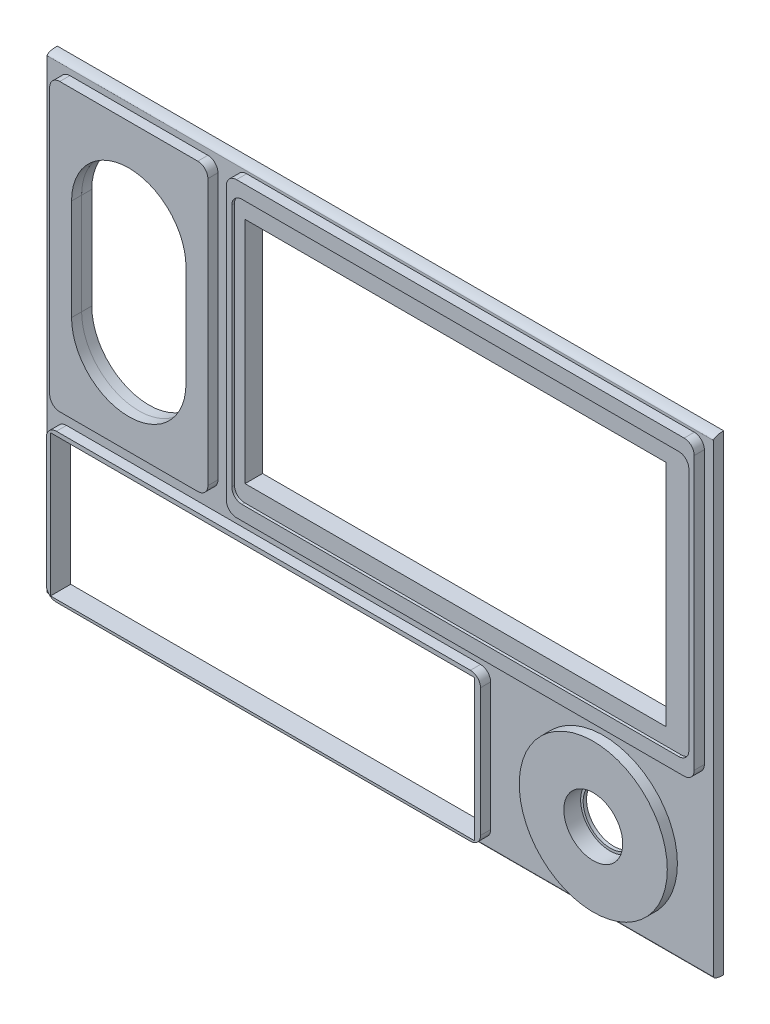
SolidWorks part; units mm, degrees
ref_plane "Front Plane" through (0, 0, 0) normal (0, 0, 1) x (1, 0, 0)
ref_plane "Top Plane" through (0, 0, 0) normal (0, 1, 0) x (1, 0, 0)
ref_plane "Right Plane" through (0, 0, 0) normal (1, 0, 0) x (0, 0, -1)
sketch "Sketch1" plane through (0, 0, 0) normal (0, 0, 1) x (1, 0, 0)
  line L1 (99, -70) -> (-99, -70)
  line L2 (99, -70) -> (99, 70)
  line L3 (99, 70) -> (-99, 70)
  line L4 (-99, -70) -> (-99, 70)
  line L5 (99, -70) -> (-99, 70) construction
  line L6 (99, 70) -> (-99, -70) construction
  point P0 (0, 0)
  dimension "D1" = 198
  dimension "D2" = 140
extrude "main_body" add sketch "Sketch1" along normal blind 3
fillet "long_corners" radius 3 2 edges at (0, 70, 3) (0, -70, 3) second distance 1 first distance on face at (0, 70, 1.5) first distance on face at (0, -70, 1.5)
sketch "Sketch2" plane through (0, 0, 3) normal (0, 0, 1) x (1, 0, 0)
  line L0 (-99, 24.75) -> (99, 24.75) construction
  line L1 (-99, 69) -> (-99, -69) construction
  line L2 (99, -69) -> (99, 69) construction
  line L3 (99, 69) -> (-99, 69) construction
  line L4 (-48.25, -17.75) -> (-95.25, -17.75)
  line L5 (-48.25, -17.75) -> (-48.25, 67.25)
  line L6 (-48.25, 67.25) -> (-95.25, 67.25)
  line L7 (-95.25, -17.75) -> (-95.25, 67.25)
  line L8 (-48.25, -17.75) -> (-95.25, 67.25) construction
  line L9 (-48.25, 67.25) -> (-95.25, -17.75) construction
  point P6 (-71.75, 24.75)
  dimension "D1" = 85
  dimension "D2" = 47
  dimension "D3" = 27.25
  dimension "D4" = 44.25
extrude "speaker" add sketch "Sketch2" along normal blind 3
fillet "speaker_corners" radius 3 4 edges at (-95.25, 67.25, 4.5) (-95.25, -17.75, 4.5) (-48.25, -17.75, 4.5) (-48.25, 67.25, 4.5)
sketch "Sketch3" plane through (0, 0, 3) normal (0, 0, 1) x (1, 0, 0)
  line L0 (-99, 24.75) -> (99, 24.75) construction
  line L1 (-99, 69) -> (-99, -69) construction
  line L2 (99, -69) -> (99, 69) construction
  line L4 (-48.25, -14.75) -> (-48.25, 64.25) construction
  line L5 (96.25, -18.75) -> (-42.75, -18.75)
  line L6 (96.25, -18.75) -> (96.25, 68.25)
  line L7 (96.25, 68.25) -> (-42.75, 68.25)
  line L8 (-42.75, -18.75) -> (-42.75, 68.25)
  line L9 (96.25, -18.75) -> (-42.75, 68.25) construction
  line L10 (96.25, 68.25) -> (-42.75, -18.75) construction
  line L11 (99, 70) -> (-99, 70) construction
  point P8 (26.75, 24.75)
  dimension "D1" = 1.75
  dimension "D2" = 87
  dimension "D3" = 139
  dimension "D4" = 2.75
  dimension "D5" = 5.5
extrude "lcd" add sketch "Sketch3" along normal blind 3
fillet "lcd_corners" radius 3 4 edges at (96.25, -18.75, 4.5) (-42.75, -18.75, 4.5) (96.25, 68.25, 4.5) (-42.75, 68.25, 4.5)
sketch "Sketch4" plane through (0, 0, 3) normal (0, 0, 1) x (1, 0, 0)
  line L0 (-99, -45.25) -> (99, -45.25) construction
  line L1 (-99, 69) -> (-99, -69) construction
  line L2 (99, -69) -> (99, 69) construction
  line L4 (-92.25, -17.75) -> (-51.25, -17.75) construction
  line L5 (32.75, -67.25) -> (-96.25, -67.25)
  line L6 (32.75, -67.25) -> (32.75, -23.25)
  line L7 (32.75, -23.25) -> (-96.25, -23.25)
  line L8 (-96.25, -67.25) -> (-96.25, -23.25)
  line L9 (32.75, -67.25) -> (-96.25, -23.25) construction
  line L10 (32.75, -23.25) -> (-96.25, -67.25) construction
  line L11 (-99, -70) -> (99, -70) construction
  point P8 (-31.75, -45.25)
  dimension "D1" = 2.75
  dimension "D2" = 129
  dimension "D3" = 44
  dimension "D4" = 2.75
  dimension "D5" = 5.5
extrude "keypad" add sketch "Sketch4" along normal blind 3
fillet "keypad_corners" radius 3 4 edges at (-96.25, -67.25, 4.5) (32.75, -67.25, 4.5) (32.75, -23.25, 4.5) (-96.25, -23.25, 4.5)
sketch "Sketch5" plane through (0, 0, 3) normal (0, 0, 1) x (1, 0, 0)
  line L0 (32.75, -45.25) -> (99, -45.25) construction
  line L1 (32.75, -64.25) -> (32.75, -26.25) construction
  line L2 (99, -69) -> (99, 69) construction
  circle A0 centre (66.25, -45.25) radius 22
  dimension "D1" = 44
  dimension "D2" = 32.75
  dimension "D3" = 33.5
extrude "vfo" add sketch "Sketch5" along normal blind 3
sketch "Sketch6" plane through (0, 0, 6) normal (0, 0, 1) x (1, 0, 0)
  line L0 (44.25, -45.25) -> (88.25, -45.25) construction
  line L2 (66.25, -23.25) -> (66.25, -67.25) construction
  line L3 (74.5, -56.25) -> (58, -56.25)
  line L4 (74.5, -56.25) -> (74.5, -34.25)
  line L5 (74.5, -34.25) -> (58, -34.25)
  line L6 (58, -56.25) -> (58, -34.25)
  line L7 (74.5, -56.25) -> (58, -34.25) construction
  line L8 (74.5, -34.25) -> (58, -56.25) construction
  circle A0 centre (66.25, -45.25) radius 22 construction
  point P7 (66.25, -45.25)
  dimension "D1" = 16.5
  dimension "D2" = 22
sketch "Sketch7" plane through (0, 0, 6) normal (0, 0, 1) x (1, 0, 0)
  line L0 (44.25, -45.25) -> (88.25, -45.25) construction
  line L1 (66.25, -23.25) -> (66.25, -67.25) construction
  circle A0 centre (66.25, -45.25) radius 22 construction
  circle A1 centre (66.25, -45.25) radius 22 construction
  circle A2 centre (66.25, -45.25) radius 8.75
  dimension "D1" = 17.5
extrude "vfo_encoder_knob_cut" cut sketch "Sketch7" against normal blind 5
sketch "Sketch16" plane through (0, 0, 0) normal (0, 0, -1) x (-1, 0, 0)
  line L0 (-99, 70) -> (99, 70) construction
  line L5 (-99, -19) -> (99, -19) construction
  line L10 (-99, -70) -> (-99, 70) construction
  line L27 (99, 70) -> (99, -70) construction
  line L28 (99, -70) -> (-99, -70) construction
  line L30 (-43, -21) -> (-69, -21)
  line L31 (-43, -21) -> (-43, -17)
  line L32 (-43, -17) -> (-69, -17)
  line L33 (-69, -21) -> (-69, -17)
  line L34 (-43, -21) -> (-69, -17) construction
  line L35 (-43, -17) -> (-69, -21) construction
  line L36 (-86.25, -23) -> (-43, -23)
  line L37 (-86.25, -23) -> (-86.25, -32)
  line L38 (-86.25, -32) -> (-43, -32)
  line L39 (-43, -23) -> (-43, -32)
  line L40 (-55, -33.25) -> (-43, -33.25)
  line L41 (-55, -33.25) -> (-55, -57.25)
  line L42 (-55, -57.25) -> (-43, -57.25)
  line L43 (-43, -33.25) -> (-43, -57.25)
  line L44 (-42, -17) -> (-32, -17)
  line L45 (-42, -17) -> (-42, -57.25)
  line L46 (-42, -57.25) -> (-32, -57.25)
  line L47 (-32, -17) -> (-32, -57.25)
  line L48 (-86.25, -33.25) -> (-77.25, -33.25)
  line L49 (-86.25, -33.25) -> (-86.25, -57.25)
  line L50 (-86.25, -57.25) -> (-77.25, -57.25)
  line L51 (-77.25, -33.25) -> (-77.25, -57.25)
  line L52 (-93, 45) -> (-87, 45)
  line L53 (-93, 45) -> (-93, 33.5)
  line L54 (-93, 33.5) -> (-87, 33.5)
  line L55 (-87, 45) -> (-87, 33.5)
  point P30 (-56, -19)
  dimension "D4" = 6
  dimension "D5" = 25
  dimension "D6" = 6
  dimension "D13" = 11.5
  dimension "D16" = 51
  dimension "D17" = 26
  dimension "D18" = 4
  dimension "D19" = 142
  dimension "D20" = 40.25
  dimension "D21" = 24
  dimension "D22" = 12.75
  dimension "D23" = 12.75
  dimension "D24" = 12
  dimension "D25" = 10
  dimension "D26" = 1
  dimension "D27" = 12.75
  dimension "D28" = 22.25
  dimension "D29" = 9
  dimension "D30" = 43.25
  dimension "D31" = 1.25
  dimension "D32" = 12.75
  dimension "D33" = 24
  dimension "D34" = 9
  dimension "D35" = 1
extrude "conn_slots" [suppressed] cut sketch "Sketch16" against normal blind 2
sketch "Sketch19" plane through (0, 0, 6) normal (0, 0, 1) x (1, 0, 0)
  line L0 (-71.75, 67.25) -> (-71.75, -17.75) construction
  line L1 (-51.25, 67.25) -> (-92.25, 67.25) construction
  line L2 (-92.25, -17.75) -> (-51.25, -17.75) construction
  line L3 (-71.75, 8.25) -> (-71.75, 38.25) construction
  line L4 (-95.25, 64.25) -> (-95.25, -14.75) construction
  line L5 (-95.25, 24.75) -> (-48.25, 24.75) construction
  line L6 (-48.25, -14.75) -> (-48.25, 64.25) construction
  line L7 (-88.75, 8.25) -> (-88.75, 38.25)
  line L8 (-54.75, 8.25) -> (-54.75, 38.25)
  arc A0 (-88.75, 8.25) -> (-54.75, 8.25) centre (-71.75, 8.25) ccw
  arc A1 (-54.75, 38.25) -> (-88.75, 38.25) centre (-71.75, 38.25) ccw
  point P14 (-71.75, 23.25)
  point P19 (-71.75, -8.75)
  point P20 (-71.75, 55.25)
  dimension "D2" = 64
  dimension "D1" = 34
  dimension "D3" = 12
extrude "speaker_cut" cut sketch "Sketch19" against normal through all
sketch "Sketch21" plane through (0, 0, 0) normal (0, 0, -1) x (-1, 0, 0)
  line L0 (71.75, -8.75) -> (71.75, 55.25) construction
  line L2 (54.75, 8.25) -> (54.75, 38.25) construction
  line L3 (54.75, 23.25) -> (88.75, 23.25) construction
  line L4 (88.75, 38.25) -> (88.75, 8.25) construction
  line L5 (50.25, 59.25) -> (93.25, 59.25)
  line L6 (50.25, 59.25) -> (50.25, -12.75)
  line L7 (50.25, -12.75) -> (93.25, -12.75)
  line L8 (93.25, 59.25) -> (93.25, -12.75)
  line L9 (50.25, 59.25) -> (93.25, -12.75) construction
  line L10 (50.25, -12.75) -> (93.25, 59.25) construction
  arc A0 (54.75, 8.25) -> (88.75, 8.25) centre (71.75, 8.25) ccw construction
  arc A1 (88.75, 38.25) -> (54.75, 38.25) centre (71.75, 38.25) ccw construction
  point P14 (71.75, 23.25)
  dimension "D1" = 43
  dimension "D2" = 72
extrude "speaker_slot" cut sketch "Sketch21" against normal blind 3
sketch "Sketch9" plane through (0, 0, 6) normal (0, 0, 1) x (1, 0, 0)
  line L0 (-42.75, 24.75) -> (96.25, 24.75) construction
  line L1 (-42.75, 65.25) -> (-42.75, -15.75) construction
  line L2 (96.25, -15.75) -> (96.25, 65.25) construction
  line L3 (-39.75, -18.75) -> (93.25, -18.75) construction
  line L4 (94.65, -14.5) -> (-41.15, -14.5)
  line L5 (94.65, -14.5) -> (94.65, 64)
  line L6 (94.65, 64) -> (-41.15, 64)
  line L7 (-41.15, -14.5) -> (-41.15, 64)
  line L8 (94.65, -14.5) -> (-41.15, 64) construction
  line L9 (94.65, 64) -> (-41.15, -14.5) construction
  line L10 (93.25, 68.25) -> (-39.75, 68.25) construction
  line L11 (96.25, -15.75) -> (96.25, 65.25) construction
  point P6 (26.75, 24.75)
  dimension "D1" = 135.8
  dimension "D2" = 78.5
  dimension "D3" = 1.6
  dimension "D4" = 4.25
  dimension "D5" = 4.25
  dimension "D6" = 1.6
extrude "lcd_front" cut sketch "Sketch9" against normal blind 0.8
sketch "Sketch10" plane through (0, 0, 0) normal (0, 0, -1) x (-1, 0, 0)
  line L0 (-94.65, -14.5) -> (-94.65, 64) construction
  line L1 (-94.65, 64) -> (41.15, 64) construction
  line L2 (41.15, 64) -> (41.15, -14.5) construction
  line L3 (-94.65, 64) -> (41.15, 64) construction
  line L4 (38, -9.5) -> (-87, -9.5)
  line L5 (38, -9.5) -> (38, 58.5)
  line L6 (38, 58.5) -> (-87, 58.5)
  line L7 (-87, -9.5) -> (-87, 58.5)
  line L8 (-87, -9.5) -> (38, 58.5) construction
  line L9 (-87, 58.5) -> (38, -9.5) construction
  line L10 (-99, -70) -> (-99, 70) construction
  line L11 (-99, 70) -> (99, 70) construction
  line L13 (41.15, -14.5) -> (-94.65, -14.5) construction
  dimension "D1" = 125
  dimension "D2" = 68
  dimension "D3" = 12
  dimension "D4" = 3.15
  dimension "D5" = 11.5
  dimension "D6" = 5.5
  dimension "D7" = 7.65
  dimension "D8" = 5.5
  dimension "D9" = 5
fillet "speaker_slot_corners" [suppressed] radius 3
sketch "Sketch24" plane through (0, 0, 3) normal (0, 0, 1) x (1, 0, 0)
  line L0 (99, -69) -> (99, 69) construction
  line L1 (99, 68.5) -> (98, 68.5)
  line L2 (99, 68.5) -> (99, -67.5)
  line L3 (99, -67.5) -> (98, -67.5)
  line L4 (98, 68.5) -> (98, -67.5)
  line L5 (-99, -69) -> (99, -69) construction
  line L6 (-98, -69) -> (98, -69)
  line L7 (-98, -69) -> (-98, -68)
  line L8 (-98, -68) -> (98, -68)
  line L9 (98, -69) -> (98, -68)
  line L10 (-99, 69) -> (-99, -69) construction
  line L12 (-99, 69) -> (-98, 69)
  line L13 (-99, 69) -> (-99, -67)
  line L14 (-99, -67) -> (-98, -67)
  line L15 (-98, 69) -> (-98, -67)
  line L16 (38, -19.5) -> (39, -19.5)
  line L17 (38, -19.5) -> (38, -67.5)
  line L18 (38, -67.5) -> (39, -67.5)
  line L19 (39, -19.5) -> (39, -67.5)
  line L20 (92, -19.5) -> (93, -19.5)
  line L21 (92, -19.5) -> (92, -67.5)
  line L22 (92, -67.5) -> (93, -67.5)
  line L23 (93, -19.5) -> (93, -67.5)
  dimension "D1" = 196
  dimension "D2" = 1
  dimension "D3" = 136
  dimension "D4" = 1
  dimension "D5" = 1
  dimension "D6" = 1.5
  dimension "D7" = 136
  dimension "D8" = 1
  dimension "D9" = 1
  dimension "D10" = 1
  dimension "D11" = 48
  dimension "D12" = 48
  dimension "D13" = 1.5
  dimension "D14" = 1.5
  dimension "D15" = 6
  dimension "D16" = 60
extrude "3D_supports" [suppressed] add sketch "Sketch24" along normal blind 3
sketch "Sketch25" plane through (0, 0, 6) normal (0, 0, 1) x (1, 0, 0)
  line L0 (-96.25, -30.25) -> (32.75, -30.25) construction
  line L1 (29.75, -23.25) -> (-93.25, -23.25) construction
  line L2 (-93.25, -67.25) -> (29.75, -67.25) construction
  line L3 (-77, -23.25) -> (-77, -67.25) construction
  line L5 (-35.4, -64) -> (32.75, -64) construction
  line L6 (-96.25, -26.25) -> (-96.25, -64.25) construction
  line L11 (32.75, -64.25) -> (32.75, -26.25) construction
  line L12 (-58.7, -23.25) -> (-58.7, -67.25) construction
  line L13 (-96.25, -40.25) -> (32.75, -40.25) construction
  line L14 (29.75, -23.25) -> (-93.25, -23.25) construction
  line L15 (-40.4, -23.25) -> (-40.4, -67.25) construction
  line L16 (-93.25, -67.25) -> (29.75, -67.25) construction
  line L17 (-72, -34) -> (-82, -34)
  line L18 (-22.1, -23.25) -> (-22.1, -67.25) construction
  line L19 (-96.25, -50.25) -> (32.75, -50.25) construction
  line L20 (-3.8, -23.25) -> (-3.8, -67.25) construction
  line L21 (-72, -34) -> (-72, -26.5)
  line L22 (14.5, -23.25) -> (14.5, -67.25) construction
  line L23 (-96.25, -26.25) -> (-96.25, -64.25) construction
  line L24 (-96.25, -60.25) -> (32.75, -60.25) construction
  line L25 (-72, -26.5) -> (-82, -26.5)
  line L26 (-82, -34) -> (-82, -26.5)
  line L27 (-72, -34) -> (-82, -26.5) construction
  line L28 (-72, -26.5) -> (-82, -34) construction
  line L29 (-72, -44) -> (-82, -44)
  line L30 (-72, -44) -> (-72, -36.5)
  line L31 (-72, -36.5) -> (-82, -36.5)
  line L32 (-82, -44) -> (-82, -36.5)
  line L33 (-72, -44) -> (-82, -36.5) construction
  line L34 (-72, -36.5) -> (-82, -44) construction
  line L35 (-72, -54) -> (-82, -54)
  line L36 (-72, -54) -> (-72, -46.5)
  line L37 (-72, -46.5) -> (-82, -46.5)
  line L38 (-82, -54) -> (-82, -46.5)
  line L39 (-72, -54) -> (-82, -46.5) construction
  line L40 (-72, -46.5) -> (-82, -54) construction
  line L41 (-72, -64) -> (-82, -64)
  line L42 (-72, -64) -> (-72, -56.5)
  line L43 (-72, -56.5) -> (-82, -56.5)
  line L44 (-82, -64) -> (-82, -56.5)
  line L45 (-72, -64) -> (-82, -56.5) construction
  line L46 (-72, -56.5) -> (-82, -64) construction
  line L47 (-53.7, -34) -> (-63.7, -34)
  line L48 (-53.7, -34) -> (-53.7, -26.5)
  line L49 (-53.7, -26.5) -> (-63.7, -26.5)
  line L50 (-63.7, -34) -> (-63.7, -26.5)
  line L51 (-53.7, -34) -> (-63.7, -26.5) construction
  line L52 (-53.7, -26.5) -> (-63.7, -34) construction
  line L53 (-53.7, -44) -> (-63.7, -44)
  line L54 (-53.7, -44) -> (-53.7, -36.5)
  line L55 (-53.7, -36.5) -> (-63.7, -36.5)
  line L56 (-63.7, -44) -> (-63.7, -36.5)
  line L57 (-53.7, -44) -> (-63.7, -36.5) construction
  line L58 (-53.7, -36.5) -> (-63.7, -44) construction
  line L59 (-53.7, -54) -> (-63.7, -54)
  line L60 (-53.7, -54) -> (-53.7, -46.5)
  line L61 (-53.7, -46.5) -> (-63.7, -46.5)
  line L62 (-63.7, -54) -> (-63.7, -46.5)
  line L63 (-53.7, -54) -> (-63.7, -46.5) construction
  line L64 (-53.7, -46.5) -> (-63.7, -54) construction
  line L65 (-53.7, -64) -> (-63.7, -64)
  line L66 (-53.7, -64) -> (-53.7, -56.5)
  line L67 (-53.7, -56.5) -> (-63.7, -56.5)
  line L68 (-63.7, -64) -> (-63.7, -56.5)
  line L69 (-53.7, -64) -> (-63.7, -56.5) construction
  line L70 (-53.7, -56.5) -> (-63.7, -64) construction
  line L71 (-35.4, -34) -> (-45.4, -34)
  line L72 (-35.4, -34) -> (-35.4, -26.5)
  line L73 (-35.4, -26.5) -> (-45.4, -26.5)
  line L74 (-45.4, -34) -> (-45.4, -26.5)
  line L75 (-35.4, -34) -> (-45.4, -26.5) construction
  line L76 (-35.4, -26.5) -> (-45.4, -34) construction
  line L77 (-35.4, -44) -> (-45.4, -44)
  line L78 (-35.4, -44) -> (-35.4, -36.5)
  line L79 (-35.4, -36.5) -> (-45.4, -36.5)
  line L80 (-45.4, -44) -> (-45.4, -36.5)
  line L81 (-35.4, -44) -> (-45.4, -36.5) construction
  line L82 (-35.4, -36.5) -> (-45.4, -44) construction
  line L83 (-35.4, -54) -> (-45.4, -54)
  line L84 (-35.4, -54) -> (-35.4, -46.5)
  line L85 (-35.4, -46.5) -> (-45.4, -46.5)
  line L86 (-45.4, -54) -> (-45.4, -46.5)
  line L87 (-35.4, -54) -> (-45.4, -46.5) construction
  line L88 (-35.4, -46.5) -> (-45.4, -54) construction
  line L89 (-35.4, -64) -> (-45.4, -64)
  line L90 (-35.4, -64) -> (-35.4, -56.5)
  line L91 (-35.4, -56.5) -> (-45.4, -56.5)
  line L92 (-45.4, -64) -> (-45.4, -56.5)
  line L93 (-35.4, -64) -> (-45.4, -56.5) construction
  line L94 (-35.4, -56.5) -> (-45.4, -64) construction
  line L95 (-17.1, -34) -> (-27.1, -34)
  line L96 (-17.1, -34) -> (-17.1, -26.5)
  line L97 (-17.1, -26.5) -> (-27.1, -26.5)
  line L98 (-27.1, -34) -> (-27.1, -26.5)
  line L99 (-17.1, -34) -> (-27.1, -26.5) construction
  line L100 (-17.1, -26.5) -> (-27.1, -34) construction
  line L101 (-17.1, -44) -> (-27.1, -44)
  line L102 (-17.1, -44) -> (-17.1, -36.5)
  line L103 (-17.1, -36.5) -> (-27.1, -36.5)
  line L104 (-27.1, -44) -> (-27.1, -36.5)
  line L105 (-17.1, -44) -> (-27.1, -36.5) construction
  line L106 (-17.1, -36.5) -> (-27.1, -44) construction
  line L111 (-17.1, -54) -> (-27.1, -54)
  line L112 (-17.1, -54) -> (-17.1, -46.5)
  line L113 (-17.1, -46.5) -> (-27.1, -46.5)
  line L114 (-27.1, -54) -> (-27.1, -46.5)
  line L115 (-17.1, -54) -> (-27.1, -46.5) construction
  line L116 (-17.1, -46.5) -> (-27.1, -54) construction
  line L117 (-17.1, -64) -> (-27.1, -64)
  line L118 (-17.1, -64) -> (-17.1, -56.5)
  line L119 (-17.1, -56.5) -> (-27.1, -56.5)
  line L120 (-27.1, -64) -> (-27.1, -56.5)
  line L121 (-17.1, -64) -> (-27.1, -56.5) construction
  line L122 (-17.1, -56.5) -> (-27.1, -64) construction
  line L127 (1.2, -34) -> (-8.8, -34)
  line L128 (1.2, -34) -> (1.2, -26.5)
  line L129 (1.2, -26.5) -> (-8.8, -26.5)
  line L130 (-8.8, -34) -> (-8.8, -26.5)
  line L131 (1.2, -34) -> (-8.8, -26.5) construction
  line L132 (1.2, -26.5) -> (-8.8, -34) construction
  line L133 (19.5, -34) -> (9.5, -34)
  line L134 (19.5, -34) -> (19.5, -26.5)
  line L135 (19.5, -26.5) -> (9.5, -26.5)
  line L136 (9.5, -34) -> (9.5, -26.5)
  line L137 (19.5, -34) -> (9.5, -26.5) construction
  line L138 (19.5, -26.5) -> (9.5, -34) construction
  line L139 (1.2, -44) -> (-8.8, -44)
  line L140 (1.2, -44) -> (1.2, -36.5)
  line L141 (1.2, -36.5) -> (-8.8, -36.5)
  line L142 (-8.8, -44) -> (-8.8, -36.5)
  line L143 (1.2, -44) -> (-8.8, -36.5) construction
  line L144 (1.2, -36.5) -> (-8.8, -44) construction
  line L145 (19.5, -44) -> (9.5, -44)
  line L146 (19.5, -44) -> (19.5, -36.5)
  line L147 (19.5, -36.5) -> (9.5, -36.5)
  line L148 (9.5, -44) -> (9.5, -36.5)
  line L149 (19.5, -44) -> (9.5, -36.5) construction
  line L150 (19.5, -36.5) -> (9.5, -44) construction
  line L151 (19.5, -54) -> (9.5, -54)
  line L152 (19.5, -54) -> (19.5, -46.5)
  line L153 (19.5, -46.5) -> (9.5, -46.5)
  line L154 (9.5, -54) -> (9.5, -46.5)
  line L155 (19.5, -54) -> (9.5, -46.5) construction
  line L156 (19.5, -46.5) -> (9.5, -54) construction
  line L157 (19.5, -64) -> (9.5, -64)
  line L158 (19.5, -64) -> (19.5, -56.5)
  line L159 (19.5, -56.5) -> (9.5, -56.5)
  line L160 (9.5, -64) -> (9.5, -56.5)
  line L161 (19.5, -64) -> (9.5, -56.5) construction
  line L162 (19.5, -56.5) -> (9.5, -64) construction
  line L163 (1.2, -64) -> (-8.8, -64)
  line L164 (1.2, -64) -> (1.2, -46.5)
  line L165 (1.2, -46.5) -> (-8.8, -46.5)
  line L166 (-8.8, -64) -> (-8.8, -46.5)
  line L167 (1.2, -64) -> (-8.8, -46.5) construction
  line L168 (1.2, -46.5) -> (-8.8, -64) construction
  point P34 (-77, -30.25)
  point P39 (-77, -40.25)
  point P44 (-77, -50.25)
  point P49 (-77, -60.25)
  point P54 (-58.7, -30.25)
  point P59 (-58.7, -40.25)
  point P64 (-58.7, -50.25)
  point P69 (-58.7, -60.25)
  point P74 (-40.4, -30.25)
  point P79 (-40.4, -40.25)
  point P84 (-40.4, -50.25)
  point P89 (-40.4, -60.25)
  point P94 (-22.1, -30.25)
  point P99 (-22.1, -40.25)
  point P104 (-22.1, -50.25)
  point P109 (-22.1, -60.25)
  point P114 (-3.8, -30.25)
  point P119 (14.5, -30.25)
  point P124 (-3.8, -40.25)
  point P129 (14.5, -40.25)
  point P134 (14.5, -50.25)
  point P139 (14.5, -60.25)
  point P144 (-3.8, -55.25)
  dimension "D1" = 18.25
  dimension "D2" = 18.3
  dimension "D3" = 18.3
  dimension "D4" = 18.3
  dimension "D5" = 18.3
  dimension "D6" = 18.3
  dimension "D7" = 19.25
  dimension "D8" = 7
  dimension "D9" = 10
  dimension "D10" = 10
  dimension "D11" = 10
  dimension "D12" = 7
  dimension "D13" = 10
  dimension "D14" = 10
  dimension "D15" = 10
  dimension "D16" = 10
  dimension "D17" = 10
  dimension "D18" = 10
  dimension "D19" = 10
  dimension "D20" = 10
  dimension "D21" = 10
  dimension "D22" = 10
  dimension "D23" = 10
  dimension "D24" = 10
  dimension "D25" = 10
  dimension "D26" = 10
  dimension "D27" = 10
  dimension "D28" = 10
  dimension "D29" = 10
  dimension "D30" = 10
  dimension "D31" = 10
  dimension "D32" = 10
  dimension "D33" = 10
  dimension "D34" = 10
  dimension "D35" = 10
  dimension "D36" = 7.5
  dimension "D37" = 7.5
  dimension "D38" = 7.5
  dimension "D39" = 7.5
  dimension "D40" = 7.5
  dimension "D41" = 7.5
  dimension "D42" = 17.5
  dimension "D43" = 7.5
  dimension "D44" = 7.5
  dimension "D45" = 7.5
  dimension "D46" = 7.5
  dimension "D47" = 7.5
  dimension "D48" = 7.5
  dimension "D49" = 7.5
  dimension "D50" = 7.5
  dimension "D51" = 7.5
  dimension "D52" = 7.5
  dimension "D53" = 7.5
  dimension "D54" = 7.5
  dimension "D55" = 7.5
  dimension "D56" = 7.5
  dimension "D57" = 7.5
  dimension "D58" = 7.5
  dimension "D59" = 5
extrude "keypad_cuts" [suppressed] cut sketch "Sketch25" against normal through all
sketch "Sketch27" plane through (0, 0, 6) normal (0, 0, 1) x (1, 0, 0)
  line L0 (-71.75, 67.25) -> (-71.75, -17.75) construction
  line L1 (-51.25, 67.25) -> (-92.25, 67.25) construction
  line L2 (-92.25, -17.75) -> (-51.25, -17.75) construction
  line L3 (-51.25, 67.25) -> (-92.25, 67.25) construction
  line L4 (-95.25, 64.25) -> (-95.25, -14.75) construction
  line L5 (-95.25, 24.75) -> (-48.25, 24.75) construction
  line L6 (-48.25, -14.75) -> (-48.25, 64.25) construction
  line L7 (-49.25, -16.75) -> (-94.25, -16.75)
  line L8 (-49.25, -16.75) -> (-49.25, 66.25)
  line L9 (-49.25, 66.25) -> (-94.25, 66.25)
  line L10 (-94.25, -16.75) -> (-94.25, 66.25)
  line L11 (-49.25, -16.75) -> (-94.25, 66.25) construction
  line L12 (-49.25, 66.25) -> (-94.25, -16.75) construction
  line L13 (-92.4893, 58.2174) -> (-50.5364, 58.2174)
  line L14 (-92.4893, 58.2174) -> (-92.4893, 57.6406)
  line L15 (-92.4893, 57.6406) -> (-50.5364, 57.6406)
  line L16 (-50.5364, 58.2174) -> (-50.5364, 57.6406)
  line L17 (-92.5601, -9.7996) -> (-51.5679, -9.7996)
  line L18 (-92.5601, -9.7996) -> (-92.5601, -10.5959)
  line L19 (-92.5601, -10.5959) -> (-51.5679, -10.5959)
  line L20 (-51.5679, -9.7996) -> (-51.5679, -10.5959)
  line L21 (-92.5949, 62.3138) -> (-50.9421, 62.3138)
  line L22 (-92.5949, 62.3138) -> (-92.5949, 61.7033)
  line L23 (-92.5949, 61.7033) -> (-50.9421, 61.7033)
  line L24 (-50.9421, 62.3138) -> (-50.9421, 61.7033)
  line L25 (-92.5601, -13.9717) -> (-51.5679, -13.9717)
  line L26 (-92.5601, -13.9717) -> (-92.5601, -14.4948)
  line L27 (-92.5601, -14.4948) -> (-51.5679, -14.4948)
  line L28 (-51.5679, -13.9717) -> (-51.5679, -14.4948)
  line L29 (-89.2446, 54.8384) -> (-89.7432, 54.8384)
  line L30 (-89.2446, 54.8384) -> (-89.2446, -7.8895)
  line L31 (-89.2446, -7.8895) -> (-89.7432, -7.8895)
  line L32 (-89.7432, 54.8384) -> (-89.7432, -7.8895)
  line L33 (-54.3403, 55.8357) -> (-53.5425, 55.8357)
  line L34 (-54.3403, 55.8357) -> (-54.3403, -7.8895)
  line L35 (-54.3403, -7.8895) -> (-53.5425, -7.8895)
  line L36 (-53.5425, 55.8357) -> (-53.5425, -7.8895)
  spline S0 degree 3 poles (-85.2273, 50.796) (-89.7424, 42.1717) (-86.0053, 56.2062) (-67.6207, 56.545) (-81.6516, 54.0437) (-85.2273, 50.796) (-89.7424, 42.1717) (-86.0053, 56.2062) knots -0.491378 -0.323594 -0.106432 0 0.177703 0.508622 0.676406 0.893568 1 1.177703 1.508622 1.676406 only from (-88.4992, 44.9934) to (-88.4992, 44.9934)
  spline S1 degree 3 poles (-63.66, 54.5446) (-74.3305, 56.2002) (-63.0267, 55.444) (-59.1289, 52.2157) (-56.4007, 49.3595) (-54.5046, 42.365) (-57.1801, 48.6308) (-59.6583, 51.6302) (-63.66, 54.5446) (-74.3305, 56.2002) (-63.0267, 55.444) knots -0.398079 -0.290417 -0.157451 0 0.175094 0.301335 0.404498 0.510378 0.601921 0.709583 0.842549 1 1.175094 1.301335 1.404498 only from (-70.3805, 55.7495) to (-70.3805, 55.7495)
  spline S2 degree 3 poles (-87.7503, 2.8695) (-87.722, 0.2746) (-87.4564, -2.599) (-84.2354, -4.9619) (-81.8964, -7.0106) (-79.7934, -8.1937) (-75.5797, -9.133) (-79.6638, -7.1602) (-81.649, -6.082) (-83.7103, -4.3041) (-85.8279, -2.2071) (-86.8595, -0.9173) (-87.7503, 2.8695) (-87.722, 0.2746) (-87.4564, -2.599) knots -0.159841 -0.073288 -0.005281 0 0.150511 0.246869 0.35904 0.428265 0.508195 0.595151 0.668427 0.760608 0.840159 0.926712 0.994719 1 1.150511 1.246869 1.35904 only from (-87.7402, 1.9585) to (-87.7402, 1.9585)
  spline S3 degree 3 poles (-55.7701, -0.2134) (-55.4111, 2.4349) (-57.3796, -2.899) (-59.8384, -4.4346) (-63.0395, -7.3687) (-65.5248, -8.5457) (-70.2231, -8.9157) (-66.5639, -9.5854) (-64.4824, -8.6607) (-61.6107, -7.3068) (-59.524, -5.5966) (-57.7091, -3.7925) (-56.1943, -1.8996) (-55.7701, -0.2134) (-55.4111, 2.4349) (-57.3796, -2.899) knots -0.153945 -0.073925 -0.018433 0 0.114159 0.183695 0.297719 0.433804 0.486991 0.538135 0.621534 0.711883 0.789491 0.846055 0.926075 0.981567 1 1.114159 1.183695 1.297719 only from (-55.6236, 0.9834) to (-55.6236, 0.9834)
  point P12 (-71.75, 24.75)
  dimension "D1" = 45
  dimension "D2" = 83
  dimension "D3" = 1
  dimension "D4" = 1
extrude "speaker_grill_remove" [suppressed] cut sketch "Sketch27" against normal blind 1.5
sketch "Sketch28" plane through (0, 0, 0) normal (0, 0, -1) x (-1, 0, 0)
  line L1 (95, -66.5) -> (-31, -66.5)
  line L2 (95, -66.5) -> (95, -24.5)
  line L3 (95, -24.5) -> (-31, -24.5)
  line L4 (-31, -66.5) -> (-31, -24.5)
  line L5 (95, -66.5) -> (-31, -24.5) construction
  line L6 (95, -24.5) -> (-31, -66.5) construction
  line L21 (99, -70) -> (-99, -70) construction
  line L22 (99, 70) -> (99, -70) construction
  point P0 (32, -45.5)
  dimension "D9" = 126
  dimension "D10" = 42
  dimension "D11" = 3.5
  dimension "D12" = 4
extrude "back_channels" cut sketch "Sketch28" against normal through all
sketch "Sketch29" plane through (0, 0, 0) normal (0, 0, -1) x (-1, 0, 0)
  line L0 (-99, -70) -> (-99, 70) construction
  line L1 (-36, -68) -> (-96, -68)
  line L2 (-36, -68) -> (-36, -59)
  line L3 (-36, -59) -> (-96, -59)
  line L4 (-96, -68) -> (-96, -59)
  line L5 (-36, -68) -> (-96, -59) construction
  line L6 (-36, -59) -> (-96, -68) construction
  line L7 (99, -70) -> (-99, -70) construction
  point P0 (-66, -63.5)
  dimension "D1" = 3
  dimension "D2" = 2
  dimension "D3" = 60
  dimension "D4" = 9
extrude "logo_cut" cut sketch "Sketch29" against normal blind 2
sketch "Sketch22" plane through (0, 0, 2) normal (0, 0, -1) x (-1, 0, 0)
  line L2 (-99, -70) -> (-99, 70) construction
  line L3 (99, -70) -> (-99, -70) construction
  text T0 "KD050-042 0.1 " font "Century Gothic" height in points 22
  dimension "D1" = 5
  dimension "D2" = 4
extrude "logo_text" add sketch "Sketch22" along normal blind 1.5
sketch "Sketch30" [suppressed] plane through (0, 0, 4) normal (0, 0, -1) x (-1, 0, 0)
  line L0 (95, -24.5) -> (-31, -24.5) construction
  line L1 (30.85, -24.5) -> (31.85, -24.5)
  line L2 (30.85, -24.5) -> (30.85, -66.5)
  line L3 (30.85, -66.5) -> (31.85, -66.5)
  line L4 (31.85, -24.5) -> (31.85, -66.5)
  line L5 (-31, -66.5) -> (95, -66.5) construction
  line L6 (27.1, -26.5) -> (27.1, -34) construction
  dimension "D1" = 3.75
  dimension "D2" = 1
extrude "keypad_support" [suppressed] add sketch "Sketch30" along normal blind 4
fillet "Fillet3" [suppressed] radius 1
fillet "Fillet4" [suppressed] radius 3
fillet "Fillet1" [suppressed] radius 3
extrude "vfo_encoder_base" [suppressed] add sketch "Sketch6" against normal blind 9 from offset 6 offset against normal yes
fillet "vfo_encoder_base_corners" [suppressed] radius 3
fillet "vfo_encoder_base_support" [suppressed] radius 3
sketch "Sketch31" plane through (0, 0, 1) normal (0, 0, 1) x (1, 0, 0)
  line L0 (57.5, -45.25) -> (75, -45.25) construction
  line L1 (66.25, -36.5) -> (66.25, -54) construction
  circle A0 centre (66.25, -45.25) radius 8.75 construction
  circle A1 centre (66.25, -45.25) radius 8.75 construction
  circle A2 centre (66.25, -45.25) radius 8
  dimension "D1" = 16
extrude "vfo_encoder_bolt_cut" cut sketch "Sketch31" against normal blind 6
sketch "Sketch32" [suppressed] plane through (0, 0, -9) normal (0, 0, -1) x (-1, 0, 0)
  line L0 (-74.5, -45.25) -> (-58, -45.25) construction
  line L1 (-74.5, -37.25) -> (-74.5, -53.25) construction
  line L2 (-58, -53.25) -> (-58, -37.25) construction
  line L4 (-66.25, -34.2037) -> (-66.25, -56.25) construction
  line L5 (-61, -56.25) -> (-71.5, -56.25) construction
  circle A0 centre (-66.25, -45.25) radius 3.75
  dimension "D1" = 7.5
extrude "vfo_encoder_shaft_cut" [suppressed] cut sketch "Sketch32" against normal blind 4
sketch "Sketch34" [suppressed] plane through (0, 0, -9) normal (0, 0, -1) x (-1, 0, 0)
  line L9 (-58, -37.25) -> (-58, -53.25) construction
  line L10 (-66.25, -49) -> (-66.25, -56.25) construction
  line L11 (-71.5, -56.25) -> (-61, -56.25) construction
  line L13 (-58, -49) -> (-66.25, -49) construction
  line L14 (-64.75, -53) -> (-67.75, -53)
  line L15 (-64.75, -53) -> (-64.75, -51)
  line L16 (-64.75, -51) -> (-67.75, -51)
  line L17 (-67.75, -53) -> (-67.75, -51)
  line L18 (-64.75, -53) -> (-67.75, -51) construction
  line L19 (-64.75, -51) -> (-67.75, -53) construction
  circle A0 centre (-66.25, -45.25) radius 3.75 construction
  point P18 (-66.25, -52)
  dimension "D4" = 2
  dimension "D5" = 3
  dimension "D6" = 2
extrude "vfo_encoder_dip" [suppressed] cut sketch "Sketch34" against normal blind 1.5
fillet "Fillet6" [suppressed] radius 3
sketch "Sketch35" [suppressed] plane through (0, 0, -5) normal (0, 0, 1) x (1, 0, 0)
  line L0 (66.25, -37.25) -> (66.25, -53.25) construction
  line L1 (66.25, -53.25) -> (74.25, -45.25) construction
  line L2 (74.25, -45.25) -> (58.25, -45.25) construction
  line L8 (73.75, -45.55) -> (58.75, -45.55)
  line L13 (73.75, -45.55) -> (73.75, -44.95)
  line L14 (73.75, -44.95) -> (58.75, -44.95)
  line L15 (58.75, -45.55) -> (58.75, -44.95)
  line L16 (73.75, -45.55) -> (58.75, -44.95) construction
  line L17 (73.75, -44.95) -> (58.75, -45.55) construction
  line L18 (66.55, -44.5) -> (65.95, -44.5)
  line L19 (66.55, -44.5) -> (66.55, -38.5)
  line L20 (66.55, -38.5) -> (65.95, -38.5)
  line L21 (65.95, -44.5) -> (65.95, -38.5)
  line L22 (66.55, -44.5) -> (65.95, -38.5) construction
  line L23 (66.55, -38.5) -> (65.95, -44.5) construction
  line L24 (66.55, -52) -> (65.95, -52)
  line L25 (66.55, -52) -> (66.55, -46)
  line L26 (66.55, -46) -> (65.95, -46)
  line L27 (65.95, -52) -> (65.95, -46)
  line L28 (66.55, -52) -> (65.95, -46) construction
  line L29 (66.55, -46) -> (65.95, -52) construction
  circle A2 centre (66.25, -45.25) radius 8 construction
  circle A3 centre (66.25, -45.25) radius 8 construction
  circle A4 centre (66.25, -45.25) radius 3.75 construction
  point P9 (66.25, -45.25)
  point P14 (66.25, -41.5)
  point P23 (66.25, -49)
  dimension "D1" = 0.6
  dimension "D2" = 0.6
  dimension "D3" = 0.6
  dimension "D4" = 6
  dimension "D5" = 6
  dimension "D6" = 15
extrude "vfo_encoder_hole_supports" [suppressed] add sketch "Sketch35" along normal blind 11
fillet "Fillet7" radius 3 4 edges at (94.65, -14.5, 5.6) (94.65, 64, 5.6) (-41.15, 64, 5.6) (-41.15, -14.5, 5.6)
extrude "lcd_back" cut sketch "Sketch10" against normal through all
sketch "Sketch36" plane through (0, 0, 3) normal (0, 0, -1) x (-1, 0, 0)
  line L0 (71.7497, 67.2337) -> (71.7497, -17.8517) construction
  line L1 (71.6071, 68.2414) -> (71.6071, -18.7586) construction
  line L2 (71.6071, 7.2414) -> (71.6071, 38.2414) construction
  line L3 (71.7497, 8.2337) -> (71.7497, 38.2337) construction
  line L4 (49.1071, 23.7414) -> (96.1071, 23.7414) construction
  line L5 (48.1655, 24.6483) -> (95.1655, 24.6483) construction
  line L6 (54.7497, 8.2337) -> (54.7497, 38.2337)
  line L9 (88.7497, 8.2337) -> (88.7497, 38.2337)
  line L10 (53.6071, 7.2414) -> (53.6071, 38.2414)
  line L11 (89.6071, 7.2414) -> (89.6071, 38.2414)
  arc A0 (53.6071, 7.2414) -> (89.6071, 7.2414) centre (71.6071, 7.2414) ccw
  arc A1 (89.6071, 38.2414) -> (53.6071, 38.2414) centre (71.6071, 38.2414) ccw
  arc A4 (54.7497, 8.2337) -> (88.7497, 8.2337) centre (71.7497, 8.2337) ccw
  arc A5 (88.7497, 38.2337) -> (54.7497, 38.2337) centre (71.7497, 38.2337) ccw
  point P6 (71.7497, 23.2337)
  point P8 (0, 0)
  point P12 (71.7497, -8.7663)
  point P13 (71.7497, 55.2337)
  point P14 (71.7486, 67.1409)
  point P15 (0, 0)
  point P22 (71.6071, 22.7414)
  point P27 (71.6071, -10.7586)
  point P28 (71.6071, 56.2414)
  dimension "D1" = 34
  dimension "D2" = 64
  dimension "D3" = 12
  dimension "D4" = 36
  dimension "D5" = 67
  dimension "D6" = 12
extrude "Boss-Extrude1" add sketch "Sketch36" along normal blind 3
